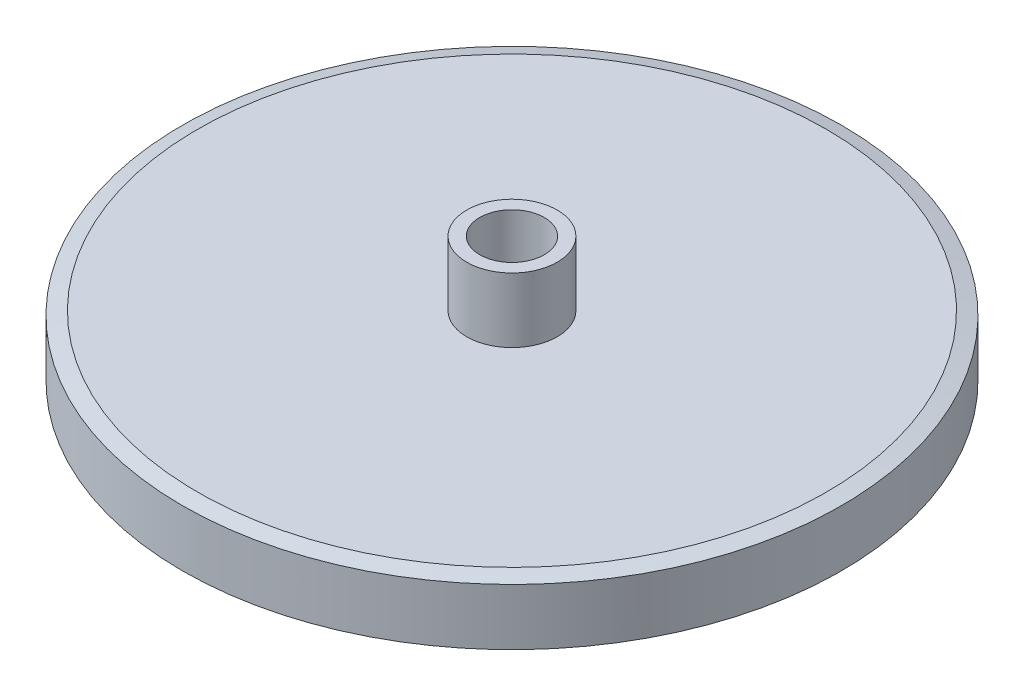
SolidWorks part; units mm, degrees
material "Сталь ШХ15 ГОСТ 801-78"
ref_plane "Plane1" through (0, 0, 0) normal (0, 0, 1) x (1, 0, 0)
ref_plane "Plane2" through (0, 0, 0) normal (0, 1, 0) x (1, 0, 0)
ref_plane "Plane3" through (0, 0, 0) normal (1, 0, 0) x (0, 0, -1)
sketch "Эскиз1" plane through (0, 0, 0) normal (0, 0, 1) x (1, 0, 0)
  line L0 (0, 0) -> (25.5, 0)
  line L1 (25.5, 0) -> (25.5, 5)
  line L2 (25.5, 5) -> (3.5, 5)
  line L3 (3.5, 5) -> (3.5, 10)
  line L4 (3.5, 10) -> (0, 10)
  line L5 (0, 10) -> (0, 0)
  dimension "D1" = 5
  dimension "30" = 25.5
  dimension "D3" = 3.5
  dimension "D4" = 5
ref_axis "Ось1" through (0, 10, 0) along (0, -1, 0)
revolve "Повернуть2" add sketch "Эскиз1" angle 360 about axis through (0, 10, 0) along (0, -1, 0)
chamfer "Фаска1" distance 1.175 angle 15 1 edges at (0, 5, 25.5) first distance on face at (0, 5, 3.5)
sketch "Эскиз2" plane through (0, 0, 0) normal (0, -1, 0) x (-1, 0, 0)
  circle A0 centre (0, 0) radius 2.5
extrude "Вырез-Вытянуть3" cut sketch "Эскиз2" against normal through all both
chamfer "Фаска2" distance 1.175 angle 15 1 edges at (0, 0, 25.5) first distance on face at (0, 0, -2.5)
